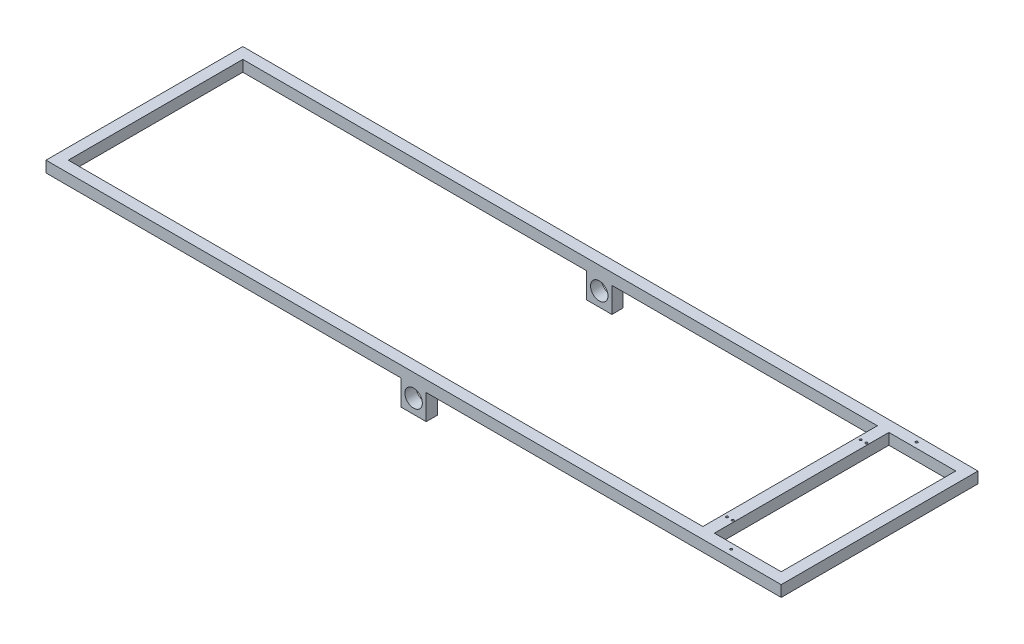
SolidWorks part; units mm, degrees
ref_plane "前视基准面" through (0, 0, 0) normal (0, 0, 1) x (1, 0, 0)
ref_plane "上视基准面" through (0, 0, 0) normal (0, 1, 0) x (1, 0, 0)
ref_plane "右视基准面" through (0, 0, 0) normal (1, 0, 0) x (0, 0, -1)
sketch "草图1" plane through (0, 0, 0) normal (0, 1, 0) x (1, 0, 0)
  line L1 (-990, 265) -> (990, 265)
  line L2 (-990, 265) -> (-990, -265)
  line L3 (-990, -265) -> (990, -265)
  line L4 (990, 265) -> (990, -265)
  line L5 (-990, 265) -> (990, -265) construction
  line L6 (-990, -265) -> (990, 265) construction
  line L7 (-960, 235) -> (960, 235)
  line L8 (-960, 235) -> (-960, -235)
  line L9 (-960, -235) -> (960, -235)
  line L10 (960, 235) -> (960, -235)
  line L11 (-960, 235) -> (960, -235) construction
  line L12 (-960, -235) -> (960, 235) construction
  point P0 (0, 0)
  point P6 (0, 0)
  dimension "D1" = 1980
  dimension "D2" = 530
  dimension "D3" = 30
  dimension "D4" = 30
extrude "凸台-拉伸1" add sketch "草图1" along normal blind 30
sketch "草图2" plane through (0, 0, 0) normal (0, -1, 0) x (1, 0, 0)
  line L0 (0, 439.6423) -> (0, -491.4203) construction
  line L1 (-990, 265) -> (990, 265) construction
  line L2 (-34, 265) -> (34, 265)
  line L3 (-34, 265) -> (-34, 235)
  line L4 (-34, 235) -> (34, 235)
  line L5 (34, 265) -> (34, 235)
  line L6 (-960, 235) -> (960, 235) construction
  line L7 (960, -235) -> (-960, -235) construction
  line L8 (-34, -235) -> (34, -235)
  line L9 (-34, -235) -> (-34, -265)
  line L10 (-34, -265) -> (34, -265)
  line L11 (34, -235) -> (34, -265)
  line L12 (990, -265) -> (-990, -265) construction
  dimension "D1" = 68
  dimension "D2" = 34
  dimension "D3" = 68
  dimension "D4" = 34
extrude "凸台-拉伸2" add sketch "草图2" along normal blind 68
sketch "草图3" plane through (0, 0, 265) normal (0, 0, 1) x (1, 0, 0)
  line L0 (34, -68) -> (-34, -68) construction
  circle A0 centre (0, -30) radius 23.5
  dimension "D1" = 47
  dimension "D2" = 38
extrude "切除-拉伸1" cut sketch "草图3" against normal through all
sketch "草图4" plane through (0, 30, 0) normal (0, 1, 0) x (1, 0, 0)
  line L0 (960, 235) -> (-960, 235) construction
  line L1 (749, 235) -> (780, 235)
  line L2 (749, 235) -> (749, -235)
  line L3 (749, -235) -> (780, -235)
  line L4 (780, 235) -> (780, -235)
  line L5 (-960, -235) -> (960, -235) construction
  line L6 (960, -235) -> (960, 235) construction
  dimension "D1" = 31
  dimension "D2" = 180
extrude "凸台-拉伸3" add sketch "草图4" against normal up to surface (30 mm away) up to face at (504.5, 0, 0)
sketch "草图5" plane through (0, 30, 0) normal (0, 1, 0) x (1, 0, 0)
  line L0 (759, 180) -> (774.5, 180) construction
  line L1 (749, 235) -> (749, -235) construction
  line L2 (780, -235) -> (780, 235) construction
  line L3 (-200.9007, 0) -> (293.2172, 0) construction
  circle A0 centre (759, 180) radius 3
  circle A1 centre (774.5, 180) radius 3
  circle A2 centre (759, -180) radius 3
  circle A3 centre (774.5, -180) radius 3
  dimension "D1" = 6
  dimension "D2" = 6
  dimension "D3" = 10
  dimension "D4" = 5.5
  dimension "D5" = 180
extrude "切除-拉伸2" cut sketch "草图5" against normal through all
sketch "草图6" plane through (0, 30, 0) normal (0, 1, 0) x (1, 0, 0)
  line L0 (900.6933, -265) -> (900.6933, -235) construction
  line L1 (-990, -265) -> (990, -265) construction
  line L2 (780, -235) -> (960, -235) construction
  line L3 (990, -265) -> (990, 265) construction
  circle A0 centre (840, -250) radius 3
  dimension "D1" = 6
  dimension "D2" = 150
extrude "切除-拉伸3" cut sketch "草图6" against normal through all and the other way through all
mirror "镜向1" about plane through (0, 0, 0) normal (0, 0, 1) of "切除-拉伸3"
